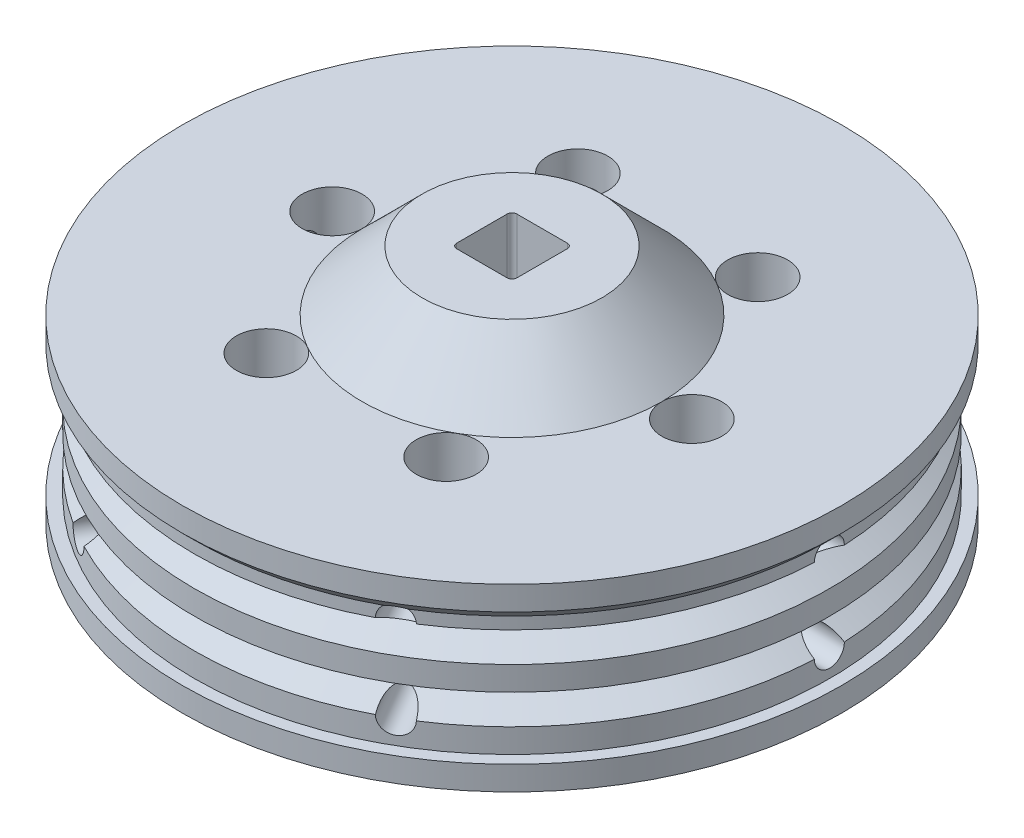
SolidWorks part; units mm, degrees
ref_plane "Front Plane" through (0, 0, 0) normal (0, 0, 1) x (1, 0, 0)
ref_plane "Top Plane" through (0, 0, 0) normal (0, 1, 0) x (1, 0, 0)
ref_plane "Right Plane" through (0, 0, 0) normal (1, 0, 0) x (0, 0, -1)
sketch "Sketch1" plane through (0, 0, 0) normal (0, 1, 0) x (1, 0, 0)
  circle A0 centre (0, 0) radius 17.4625
  circle A1 centre (0, 0) radius 20.6375 construction
  dimension "D1" = 3.175
extrude "Boss-Extrude1" add sketch "Sketch1" along normal up to surface (9.525 mm away)
sketch "Sketch2" plane through (0, 9.525, 0) normal (0, 1, 0) x (1, 0, 0)
  line L1 (-1.5938, 1.5938) -> (1.5939, 1.5938)
  line L2 (-1.5938, 1.5938) -> (-1.5938, -1.5939)
  line L3 (-1.5938, -1.5939) -> (1.5939, -1.5939)
  line L4 (1.5939, 1.5938) -> (1.5939, -1.5939)
  line L5 (-1.5938, 1.5938) -> (1.5939, -1.5939) construction
  line L6 (-1.5938, -1.5939) -> (1.5939, 1.5938) construction
  point P0 (0, 0)
  point P6 (0, 0)
  point P7 (0, 0)
  point P8 (0, 0)
  point P9 (0, 0)
  point P10 (0, 0)
  dimension "D1" = 3.1877
extrude "Cut-Extrude1" cut sketch "Sketch2" against normal through all
sketch "Sketch12" plane through (0, 9.525, 0) normal (0, 1, 0) x (1, 0, 0)
  line L0 (1.5939, 1.5938) -> (-1.5938, 1.5938)
  line L1 (-1.5938, 1.5938) -> (-1.5938, -1.5939)
  line L2 (-1.5938, -1.5939) -> (1.5939, -1.5939)
  line L3 (1.5939, -1.5939) -> (1.5939, 1.5938)
  line L4 (1.5939, -1.5939) -> (1.5939, 1.5938) construction
  line L5 (1.5939, 1.5938) -> (-1.5938, 1.5938) construction
  line L6 (-1.5938, -1.5939) -> (1.5939, -1.5939) construction
  line L7 (-1.5938, 1.5938) -> (-1.5938, -1.5939) construction
  circle A0 centre (0, 0) radius 4.7625
  point P7 (1.0841, 1.3619)
  dimension "D1" = 9.525
extrude "Boss-Extrude2" add sketch "Sketch12" along normal blind 3.175
sketch "Sketch3" plane through (0, 0, 0) normal (1, 0, 0) x (0, 0, -1)
  line L0 (-17.4625, 9.525) -> (-17.4625, 0) construction
  line L1 (-19.3675, 8.255) -> (-15.5575, 8.255)
  line L2 (-19.3675, 8.255) -> (-19.3675, 1.27)
  line L3 (-19.3675, 1.27) -> (-15.5575, 1.27)
  line L4 (-15.5575, 8.255) -> (-15.5575, 1.27)
  line L5 (-19.3675, 8.255) -> (-15.5575, 1.27) construction
  line L6 (-19.3675, 1.27) -> (-15.5575, 8.255) construction
  line L7 (17.4625, 9.525) -> (-17.4625, 9.525) construction
  point P0 (-17.4625, 4.7625)
  dimension "D1" = 1.27
  dimension "D2" = 3.81
revolve "Cut-Revolve1" cut sketch "Sketch3" angle 360 about axis through (0, 58.9164, 0) along (0, -1, 0)
ref_plane "Plane1" through (0, 0, -15.5575) normal (0, 0, -1) x (-1, 0, 0)
sketch "Sketch5" plane through (0, 0, 0) normal (1, 0, 0) x (0, 0, -1)
  line L0 (15.5575, 8.255) -> (16.8275, 8.255)
  line L1 (15.5575, 1.27) -> (15.5575, 8.255) construction
  line L2 (16.8275, 8.255) -> (16.8275, 6.985)
  line L4 (15.5575, 6.985) -> (15.5575, 8.255)
  line L5 (15.5575, 1.27) -> (15.5575, 2.54)
  line L7 (16.8275, 2.54) -> (16.8275, 1.27)
  line L8 (16.8275, 1.27) -> (15.5575, 1.27)
  line L10 (16.8275, 5.3975) -> (16.8275, 4.1275)
  line L12 (15.5575, 4.1275) -> (15.5575, 5.3975)
  line L13 (17.4625, 1.27) -> (-17.4625, 1.27) construction
  line L14 (-17.4625, 8.255) -> (17.4625, 8.255) construction
  line L15 (16.8275, 4.1275) -> (15.5575, 3.3338)
  line L16 (15.5575, 3.3338) -> (16.8275, 2.54)
  line L17 (16.8275, 5.3975) -> (15.5575, 6.1913)
  line L18 (15.5575, 6.1913) -> (16.8275, 6.985)
  line L19 (15.5575, 4.1275) -> (15.5575, 3.3338)
  line L20 (15.5575, 5.3975) -> (15.5575, 6.1913)
  line L21 (15.5575, 2.54) -> (15.5575, 3.3338)
  line L22 (15.5575, 6.1913) -> (15.5575, 6.985)
  point P17 (15.5575, 4.7625)
  point P29 (15.5575, 4.7625)
  dimension "D1" = 1.27
  dimension "D2" = 1.27
revolve "Revolve1" add sketch "Sketch5" angle 360 about axis through (0, 9.525, 0) along (0, 1, 0) region at (0, 2.1192, -16.1421) region at (0, 4.7625, -16.1111) region at (0, 7.4058, -16.1421)
chamfer "Chamfer1" distance 0.635 angle 45 1 edges at (0, 8.255, 16.8275)
sketch "Sketch6" plane through (0, 9.525, 0) normal (0, 1, 0) x (1, 0, 0)
  line L0 (0, 0) -> (9.525, 0) construction
  circle A0 centre (9.525, 0) radius 1.5875
  dimension "D1" = 3.175
  dimension "D2" = 9.525
extrude "Cut-Extrude2" cut sketch "Sketch6" against normal through all
ref_plane "Plane2" through (16.8275, 0, 0) normal (1, 0, 0) x (0, 0, -1)
sketch "Sketch8" plane through (16.8275, 0, 0) normal (1, 0, 0) x (0, 0, -1)
  line L0 (0, 0) -> (0, 9.525)
  line L2 (1.5875, 9.525) -> (-1.5875, 9.525) construction
  line L3 (-17.4625, 0) -> (17.4625, 0) construction
  circle A1 centre (0, 6.985) radius 0.7937
  circle A2 centre (0, 2.54) radius 0.7938
  point P0 (0, 3.0216)
  point P8 (0, 4.7625)
  point P10 (0, 7.9285)
  dimension "D1" = 1.5875
  dimension "D3" = 2.54
  dimension "D2" = 2.54
extrude "Cut-Extrude3" cut sketch "Sketch8" against normal up to surface and the other way through all contours L0 | L0 | L0 A1 | L0 A1 | L0 A2 | L0 A2 region at (16.8275, 2.54, 0.3369) region at (16.8275, 6.985, 0.3369) region at (16.8275, 6.985, -0.3369) region at (16.8275, 2.54, -0.3369) up to face at (9.525, 0, 1.5875)
pattern_circular "CirPattern1" count 6 over 360 about axis through (0, 9.525, 0) along (0, 1, 0) of "Cut-Extrude2", "Cut-Extrude3"
chamfer "Chamfer2" distance 3.175 angle 45 1 edges at (0, 9.525, 4.7625)
fillet "Fillet3" radius 0.254 4 edges at (-1.5938, 6.35, 1.5939) (1.5939, 6.35, 1.5939) (1.5939, 6.35, -1.5938) (-1.5938, 6.35, -1.5938)
sketch "Sketch18" plane through (0, 0, 0) normal (1, 0, 0) x (0, 0, -1)
  line L0 (0, 0) -> (0, 9.525) construction
  line L1 (0, 7.3025) -> (15.7279, -1.778)
  line L2 (-17.4625, 0) -> (17.4625, 0) construction
  line L3 (17.4625, 9.525) -> (-17.4625, 9.525) construction
  line L4 (0, 7.3025) -> (15.7279, -1.778) construction
  line L5 (15.7279, -3.81) -> (15.7279, -1.778)
  line L6 (0, 5.5245) -> (15.7279, -3.81)
  line L7 (0, 5.5245) -> (0, 7.3025)
  line L8 (0, 7.3025) -> (15.7279, -1.778)
  point P2 (0, 0)
  point P9 (0, 0)
  point P12 (0, 4.7625)
  point P14 (9.0632, -0.4701)
  point P15 (9.4737, -1.905)
  point P16 (0, 0)
  point P17 (11.6563, -3.7223)
  point P18 (8.3518, 0)
  point P19 (0, 0)
  point P20 (9.2425, -0.5736)
  point P21 (0, 0)
  point P22 (0, 5.2064)
  dimension "D1" = 60
  dimension "D2" = 2.032
  dimension "D3" = 1.778
  dimension "D4" = 1.778
  dimension "D5" = 2.54
revolve "Cut-Revolve2" cut sketch "Sketch18" angle 360 about L1 region at (0, 1.7074, -8.0387)
pattern_circular "CirPattern3" count 2 over 360 about axis through (0, 0, 0) along (0, 1, 0) of "Cut-Revolve2"
